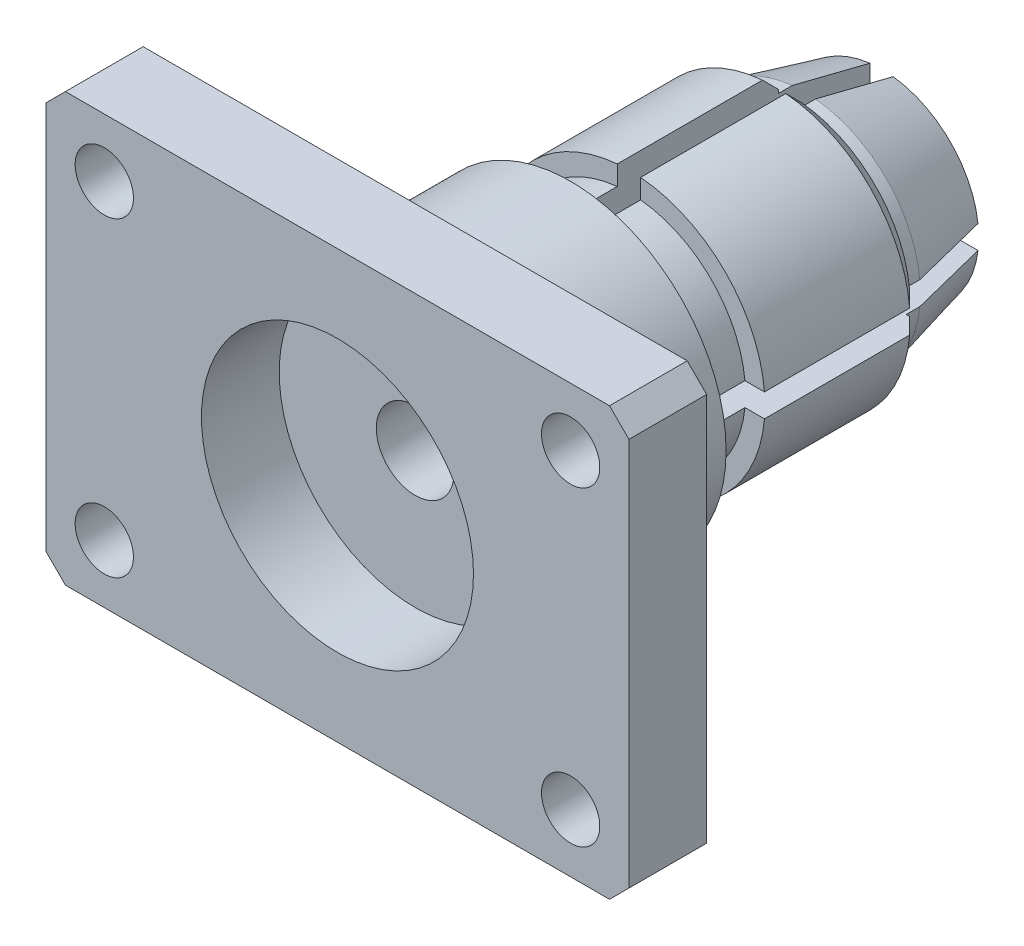
SolidWorks part; units mm, degrees
material "Латунь"
ref_plane "Спереди" through (0, 0, 0) normal (0, 0, 1) x (1, 0, 0)
ref_plane "Сверху" through (0, 0, 0) normal (0, 1, 0) x (1, 0, 0)
ref_plane "Справа" through (0, 0, 0) normal (1, 0, 0) x (0, 0, -1)
sketch "Эскиз1" plane through (0, 0, 0) normal (0, 0, 1) x (1, 0, 0)
  line L1 (-7.5, -11) -> (7.5, -11)
  line L2 (-7.5, -11) -> (-7.5, 11)
  line L3 (-7.5, 11) -> (7.5, 11)
  line L4 (7.5, -11) -> (7.5, 11)
  line L5 (-7.5, -11) -> (7.5, 11) construction
  line L6 (-7.5, 11) -> (7.5, -11) construction
  circle A0 centre (-4.5, 8) radius 1.5
  circle A1 centre (-4.5, -8) radius 1.5
  point P0 (0, 0)
  dimension "D3" = 3
  dimension "D4" = 3
  dimension "D5" = 3
  dimension "D6" = 3
  dimension "D1" = 15
  dimension "D2" = 22
extrude "Бобышка-Вытянуть1" add sketch "Эскиз1" along normal blind 4
chamfer "Фаска1" distance 1 angle 45 2 edges at (-7.5, -11, 2) (-7.5, 11, 2)
mirror "Зеркальное отражение1" about plane through (7.5, -11, 4) normal (-1, 0, 0) of "Фаска1", "Бобышка-Вытянуть1"
sketch "Эскиз2" plane through (0, 0, 0) normal (0, 0, -1) x (-1, 0, 0)
  line L0 (-7.5, -11) -> (-7.5, 0) construction
  line L1 (6.5, -11) -> (-21.5, -11) construction
  circle A0 centre (-7.5, 0) radius 2
  dimension "D1" = 4
extrude "Вырез-Вытянуть1" cut sketch "Эскиз2" against normal through all
sketch "Эскиз3" plane through (0, 0, 0) normal (0, 0, -1) x (-1, 0, 0)
  circle A0 centre (-7.5, 0) radius 8
  circle A1 centre (-7.5, 0) radius 2 construction
  circle A2 centre (-7.5, 0) radius 2
  dimension "D1" = 16
extrude "Бобышка-Вытянуть2" add sketch "Эскиз3" along normal blind 8
sketch "Эскиз4" plane through (0, 0, -8) normal (0, 0, -1) x (-1, 0, 0)
  line L1 (0.5, 0.6) -> (-15.5, 0.6)
  line L2 (0.5, 0.6) -> (0.5, -0.6)
  line L3 (0.5, -0.6) -> (-15.5, -0.6)
  line L4 (-15.5, 0.6) -> (-15.5, -0.6)
  line L5 (0.5, 0.6) -> (-15.5, -0.6) construction
  line L6 (0.5, -0.6) -> (-15.5, 0.6) construction
  line L7 (-6.9, 8) -> (-8.1, 8)
  line L8 (-6.9, 8) -> (-6.9, -8)
  line L9 (-6.9, -8) -> (-8.1, -8)
  line L10 (-8.1, 8) -> (-8.1, -8)
  line L11 (-6.9, 8) -> (-8.1, -8) construction
  line L12 (-6.9, -8) -> (-8.1, 8) construction
  circle A0 centre (-7.5, 0) radius 8 construction
  circle A1 centre (-7.5, 0) radius 6
  circle A2 centre (-7.5, 0) radius 4.5
  circle M1 centre (-7.5, 0) radius 8
  circle M2 centre (-7.5, 0) radius 2
  dimension "D1" = 12
  dimension "D2" = 9
  dimension "D3" = 1.2
extrude "Бобышка-Вытянуть3" add sketch "Эскиз4" along normal blind 16 contours A2 L10 A1 L1 | A2 L8 A1 L10 | A2 L1 A1 L8 | A2 L3 A1 L1 | A2 L8 A1 L3 | A2 L10 A1 L8 | A2 L3 A1 L10 | A2 L1 A1 L3 region at (2.2617, 0, -8) region at (4.0333, 3.4667, -8) region at (7.5, 5.2383, -8) region at (4.0333, -3.4667, -8) region at (10.9667, 3.4667, -8) region at (7.5, -5.2383, -8) region at (12.7383, 0, -8) region at (10.9667, -3.4667, -8)
chamfer "Фаска2" distance 4 distance2 1 1 edges at (1.5, 0, -24) first distance on face at (1.5, 0, -24)
sketch "Эскиз5" plane through (0, 0, -8) normal (0, 0, -1) x (-1, 0, 0)
  circle A0 centre (-7.5, 0) radius 7
  circle A1 centre (-7.5, 0) radius 4.5 construction
  circle A2 centre (-7.5, 0) radius 4.5
  dimension "D1" = 14
extrude "Бобышка-Вытянуть4" add sketch "Эскиз5" along normal blind 8.3 from offset 3
cosmetic thread "Условное изображение резьбы1" parameters "D2"=12.344
chamfer "Фаска3" distance 0.828 angle 45 1 edges at (0.5, 0, -19.3)
sketch "Эскиз6" plane through (0, 0, -24) normal (0, 0, -1) x (-1, 0, 0)
  circle A0 centre (-7.5, 0) radius 3.4455
  circle A1 centre (-7.5, 0) radius 4.5 construction
  circle A2 centre (-7.5, 0) radius 4.5
  dimension "D1" = 6.891
extrude "Бобышка-Вытянуть5" add sketch "Эскиз6" against normal offset from surface (11.8 mm away) 4.2 up to face at (3, 0, -8)
cosmetic thread "Условное изображение резьбы2" parameters "D2"=8
chamfer "Фаска4" distance 0.5545 angle 45 1 edges at (4.0545, 0, -24)
extrude "Вырез-Вытянуть3" cut sketch "Эскиз4<4>" along normal through all contours A1 L8 L10 M1 | A2 L8 A1 L10 | L8 A2 L10 M2 | A1 L3 L1 M1 | A2 L3 A1 L1 | L3 A2 L1 M2 | A1 L1 L3 M1 | A2 L1 A1 L3 | L1 A2 L3 M2 | A1 L10 L8 M1 | A2 L10 A1 L8 | L10 A2 L8 M2 region at (0.5088, 0, -8) region at (2.2617, 0, -8) region at (7.5, 6.9912, -8) region at (4.272, 0, -8) region at (7.5, 5.2383, -8) region at (7.5, -6.9912, -8) region at (7.5, 3.228, -8) region at (7.5, -5.2383, -8) region at (14.4912, 0, -8) region at (12.7383, 0, -8) region at (7.5, -3.228, -8) region at (10.728, 0, -8)
sketch "Эскиз4<4>" plane through (0, 0, -8) normal (0, 0, -1) x (-1, 0, 0) same geometry as "Эскиз4"
sketch "Эскиз7" plane through (0, 0, 4) normal (0, 0, 1) x (1, 0, 0)
  circle A0 centre (7.5, 0) radius 7
  dimension "D1" = 14
extrude "Вырез-Вытянуть4" cut sketch "Эскиз7" against normal blind 4
